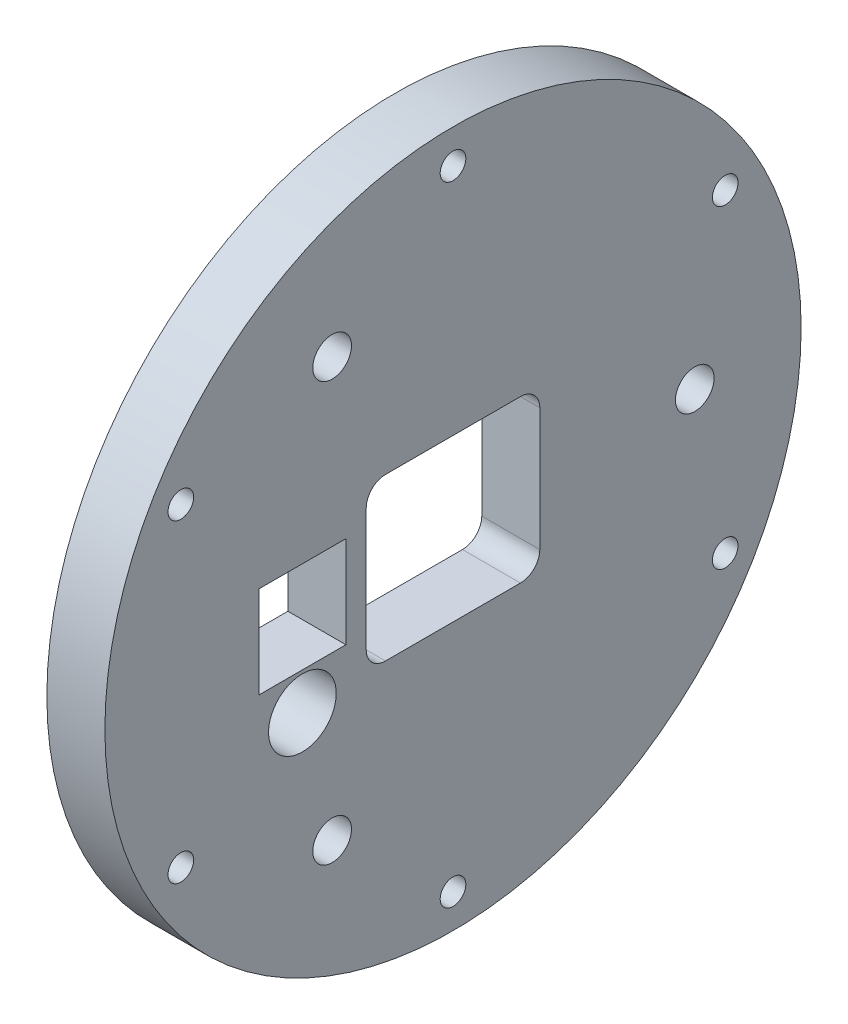
SolidWorks part; units mm, degrees
ref_plane "Front Plane" through (0, 0, 0) normal (0, 0, 1) x (1, 0, 0)
ref_plane "Top Plane" through (0, 0, 0) normal (0, 1, 0) x (1, 0, 0)
ref_plane "Right Plane" through (0, 0, 0) normal (1, 0, 0) x (0, 0, -1)
sketch "Sketch4" plane through (0, 0, 0) normal (1, 0, 0) x (0, 0, -1)
  circle A0 centre (0, 0) radius 72
  point P4 (0, 0)
  point P5 (0, 0)
  dimension "D1" = 144
sketch "Sketch2" plane through (0, 0, 0) normal (1, 0, 0) x (0, 0, -1)
  line L0 (0, 0) -> (0, 77.0354) construction
  circle A0 centre (0, 0) radius 65 construction
  circle A1 centre (0, 65) radius 2.65
  circle A2 centre (56.2917, 32.5) radius 2.65
  circle A3 centre (56.2917, -32.5) radius 2.65
  circle A4 centre (0, -65) radius 2.65
  circle A5 centre (-56.2917, -32.5) radius 2.65
  circle A6 centre (-56.2917, 32.5) radius 2.65
  point P5 (0, 65)
  point P17 (0, 0)
  dimension "D3" = 5.3
  dimension "D1" = 65
  dimension "D2" = 6
sketch "Sketch3" plane through (0, 0, 0) normal (1, 0, 0) x (0, 0, -1)
  line L0 (-4.7792, 0) -> (94.0848, 0) construction
  circle A2 centre (50, 0) radius 4
  circle A3 centre (-25, -43.3013) radius 4
  circle A4 centre (-25, 43.3013) radius 4
  point P3 (50, 0)
  dimension "D1" = 50
  dimension "D3" = 8
  dimension "D5" = 3
extrude "Boss-Extrude3" add sketch "Sketch4" along normal blind 12
extrude "Cut-Extrude6" cut sketch "Sketch3" along normal through all
extrude "Cut-Extrude1" cut sketch "Sketch2" along normal through all
sketch "Sketch1" plane through (0, 0, 0) normal (1, 0, 0) x (0, 0, -1)
  line L0 (-72, 0) -> (72, 0) construction
  line L1 (-13.95, 16.7) -> (13.95, 16.7)
  line L2 (-17.95, 12.7) -> (-17.95, -12.7)
  line L3 (-13.95, -16.7) -> (13.95, -16.7)
  line L4 (17.95, 12.7) -> (17.95, -12.7)
  line L5 (72.7609, -17.4) -> (-66.8201, -17.4) construction
  line L6 (-31.15, -17.4) -> (-31.15, 22.2578) construction
  line L7 (-40.15, 9.3) -> (-22.15, 9.3)
  line L8 (-40.15, 9.3) -> (-40.15, -9.7)
  line L9 (-40.15, -9.7) -> (-22.15, -9.7)
  line L10 (-22.15, 9.3) -> (-22.15, -9.7)
  line L11 (0, 8.4141) -> (0, -10.5859) construction
  line L12 (0, 0) -> (-23.1273, 0) construction
  circle A1 centre (-31.15, -17.4) radius 7
  arc A5 (-13.95, -16.7) -> (-17.95, -12.7) centre (-13.95, -12.7) cw
  arc A6 (13.95, -16.7) -> (17.95, -12.7) centre (13.95, -12.7) ccw
  arc A7 (17.95, 12.7) -> (13.95, 16.7) centre (13.95, 12.7) ccw
  arc A8 (-13.95, 16.7) -> (-17.95, 12.7) centre (-13.95, 12.7) ccw
  point P2 (0, 0)
  point P4 (29.5444, -6.4437)
  point P5 (-31.45, -17.7)
  point P13 (-13.95, 16.7)
  point P29 (-17.95, -16.7)
  point P32 (17.95, -16.7)
  point P35 (17.95, 16.7)
  point P38 (-17.95, 16.7)
  dimension "D2" = 35.9
  dimension "D7" = 14
  dimension "D12" = 4
  dimension "D6" = 33.4
  dimension "D8" = 13.2
  dimension "D9" = 18
  dimension "D10" = 19
  dimension "D11" = 7.7
  dimension "D13" = 0.7
extrude "gopro" cut sketch "Sketch1" along normal through all
